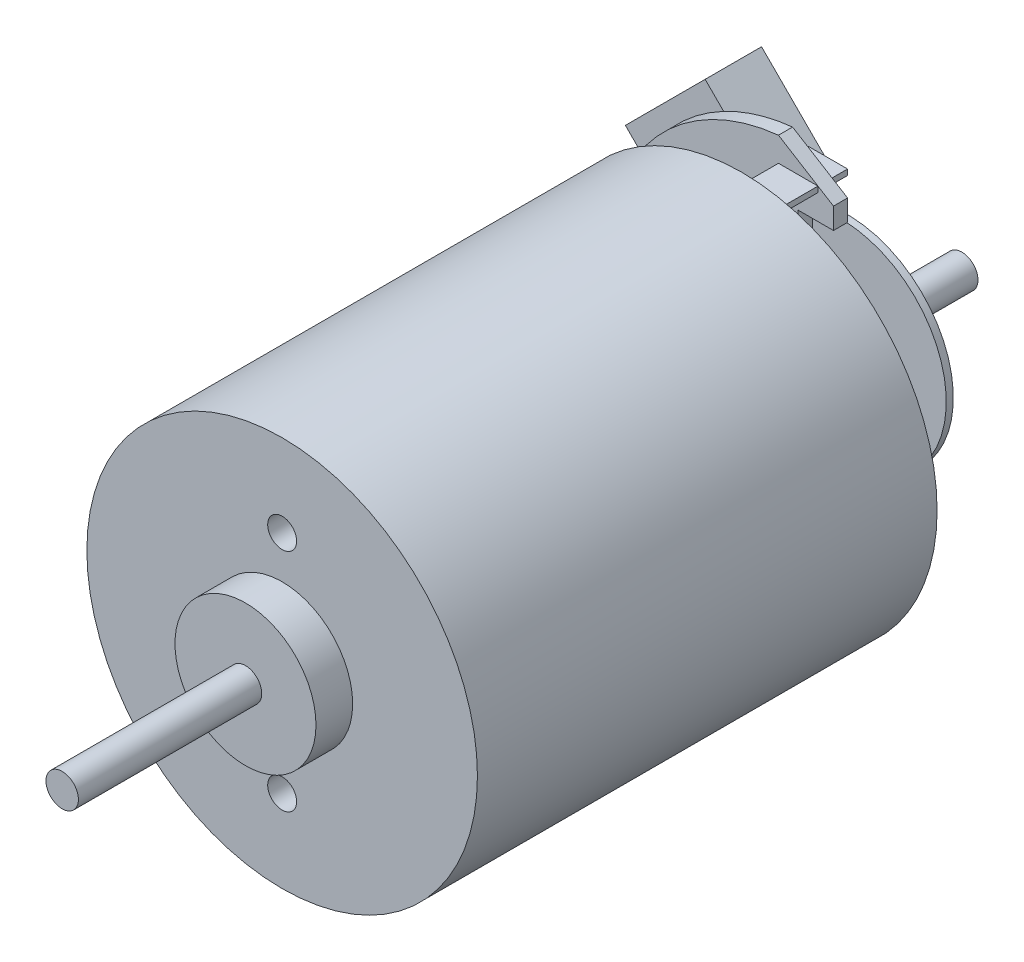
SolidWorks part; units mm, degrees
ref_plane "Front" through (0, 0, 0) normal (0, 0, 1) x (1, 0, 0)
ref_plane "Top" through (0, 0, 0) normal (0, 1, 0) x (1, 0, 0)
ref_plane "Right" through (0, 0, 0) normal (1, 0, 0) x (0, 0, -1)
sketch "Sketch1" plane through (0, 0, 0) normal (0, 0, 1) x (1, 0, 0)
  circle A0 centre (0, 0) radius 13.85
  dimension "D1" = 27.7
extrude "MAINBODY" add sketch "Sketch1" along normal blind 16.3 and the other way blind 16.3
sketch "Sketch2" plane through (0, 0, 16.3) normal (0, 0, 1) x (1, 0, 0)
  circle A0 centre (0, 0) radius 5
  circle A1 centre (0, 0) radius 1.15
  dimension "D1" = 10
  dimension "D2" = 2.3
extrude "OUTPUTSHAFT" add sketch "Sketch2" along normal blind 15.6 contours A1 region at (0, 0, 16.3)
extrude "OUTPUTBOSS" add sketch "Sketch2<3>" along normal blind 2.6 contours A0 A1 region at (-4.8586, 0, 16.3)
sketch "Sketch2<3>" plane through (0, 0, 16.3) normal (0, 0, 1) x (1, 0, 0) same geometry as "Sketch2"
hole_wizard "M2.5x0.45 Tapped Hole1" positions "Sketch7" profile "Sketch6" tap size "M2.5x0.45" standard "ANSI Metric"
sketch "Sketch7" plane through (0, 0, 16.3) normal (0, 0, 1) x (1, 0, 0)
  line L0 (0, 8) -> (0, -8) construction
  point P0 (0, 8)
  point P2 (0, -8)
  dimension "D2" = 16
sketch "Sketch6" plane through (0, 8, 16.3) normal (1, 0, 0) x (0, -1, 0)
  line L0 (0, 0) -> (0, 6.9659)
  line L1 (0, 6.9659) -> (1.025, 6.35)
  line L2 (1.025, 6.35) -> (1.025, 0)
  line L5 (1.025, 0) -> (0, 0)
  line L10 (0, 6.9659) -> (-1.025, 6.35) construction
  line L11 (0, -6.35) -> (0, 107.95) construction
  dimension "Tap Drill Dia." = 2.05
  dimension "Tap Drill Depth" = 6.35
  dimension "Drill Angle" = 118
cosmetic thread "Hole Thread1" parameters "D1"=5, "D2"=2.5
cosmetic thread "Hole Thread2" parameters "D1"=5, "D2"=2.5
mirror "REARSHAFT" about plane through (0, 0, 0) normal (0, 0, 1) of "OUTPUTBOSS", "OUTPUTSHAFT"
sketch "Sketch5" plane through (0, 0, -16.3) normal (0, 0, -1) x (-1, 0, 0)
  line L0 (0, 13.85) -> (0, -13.85) construction
  line L2 (-1.4, 11.3) -> (1.4, 11.3)
  line L3 (-1.4, 11.3) -> (-1.4, 11.7)
  line L4 (-1.4, 11.7) -> (1.4, 11.7)
  line L5 (1.4, 11.3) -> (1.4, 11.7)
  line L6 (-1.4, 11.3) -> (1.4, 11.7) construction
  line L7 (-1.4, 11.7) -> (1.4, 11.3) construction
  line L8 (-1.4, -11.7) -> (1.4, -11.7)
  line L9 (-1.4, -11.7) -> (-1.4, -11.3)
  line L10 (-1.4, -11.3) -> (1.4, -11.3)
  line L11 (1.4, -11.7) -> (1.4, -11.3)
  line L12 (-1.4, -11.7) -> (1.4, -11.3) construction
  line L13 (-1.4, -11.3) -> (1.4, -11.7) construction
  circle A0 centre (0, 0) radius 13.85 construction
  point P5 (0, 11.5)
  point P10 (0, -11.5)
  dimension "D1" = 11.3
  dimension "D2" = 11.3
  dimension "D3" = 0.4
  dimension "D4" = 2.8
extrude "TERMINALS" add sketch "Sketch5" along normal blind 6.1
sketch "Sketch8" plane through (0, 0, -16.3) normal (0, 0, -1) x (-1, 0, 0)
  line L0 (1.4, 13.4272) -> (-2.5, 11.0215)
  line L1 (-2.5, 11.0215) -> (-2.5, 9.5215)
  line L2 (-2.5, 9.5215) -> (0, 9.5215)
  line L3 (0, 9.5215) -> (0, 5)
  line L4 (-5, 0) -> (5, 0) construction
  line L5 (1.4, -13.4272) -> (-2.5, -11.0215)
  line L6 (-2.5, -11.0215) -> (-2.5, -9.5215)
  line L7 (-2.5, -9.5215) -> (0, -9.5215)
  line L8 (0, -9.5215) -> (0, -5)
  line L9 (0, 5) -> (0, -5) construction
  arc A0 (1.4, 13.4272) -> (1.4, -13.4272) centre (0, 0) cw
  arc A1 (0, -5) -> (0, 5) centre (0, 0) ccw
  circle A2 centre (0, 0) radius 5 construction
  circle A3 centre (0, 0) radius 5 construction
  dimension "D1" = 13.5
  dimension "D2" = 1.5
  dimension "D3" = 2.5
extrude "PCB" add sketch "Sketch8" along normal blind 1 from offset 4
sketch "Sketch9" plane through (0, 0, -16.3) normal (0, 0, -1) x (-1, 0, 0)
  circle A0 centre (0, 0) radius 7.5
  dimension "D1" = 15
extrude "ENCODER" add sketch "Sketch9" along normal blind 0.5 from offset 7
sketch "Sketch10" plane through (0, 0, -21.3) normal (0, 0, -1) x (-1, 0, 0)
  line L0 (2.6514, 8.3088) -> (8.3083, 2.6519)
  line L1 (2.6514, 8.3088) -> (7.6011, 13.2585)
  line L2 (8.3083, 2.6519) -> (13.258, 7.6017)
  line L3 (7.6011, 13.2585) -> (13.258, 7.6017)
  line L4 (1.4, 11.7) -> (1.4, 11.3) construction
  dimension "D1" = 7
  dimension "D2" = 8
  dimension "D3" = 3
  dimension "D4" = 45
  dimension "D5" = 7.75
extrude "CONNECTOR" add sketch "Sketch10" along normal blind 4 contours L1 L3 L2 L0
